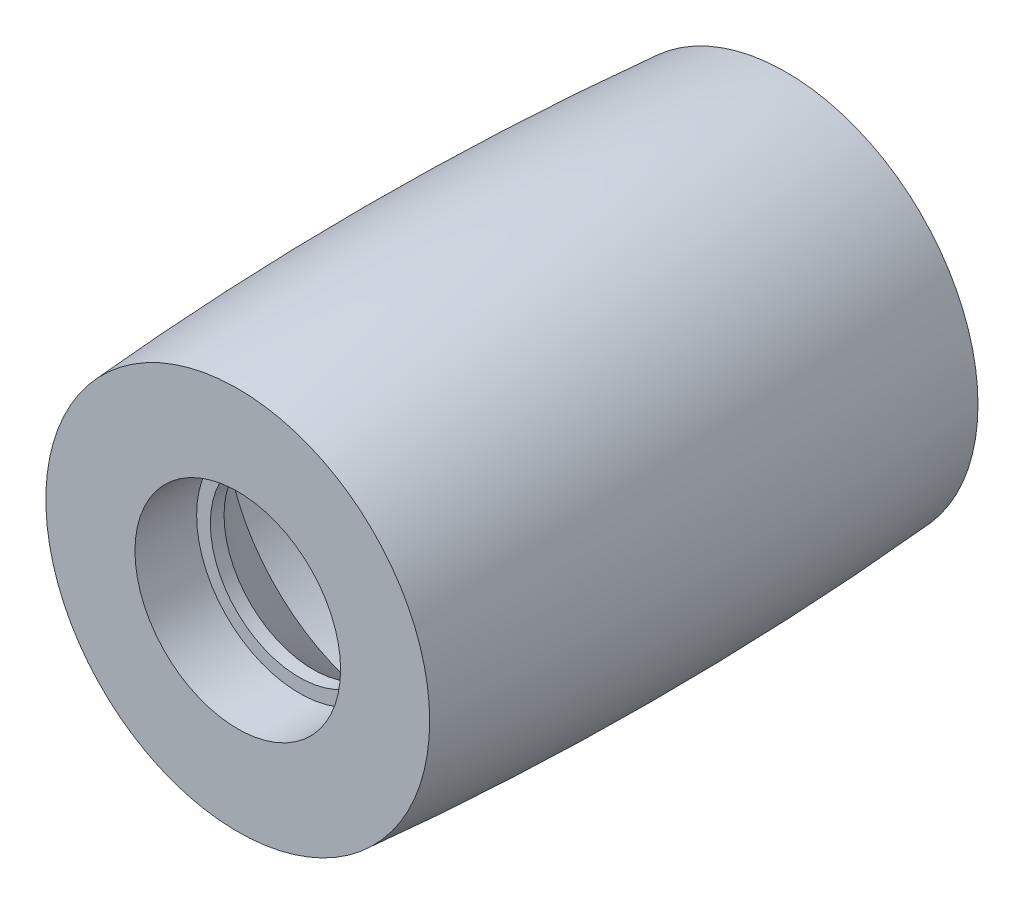
SolidWorks part; units mm, degrees
ref_plane "Ebene vorne" through (0, 0, 0) normal (0, 0, 1) x (1, 0, 0)
ref_plane "Ebene oben" through (0, 0, 0) normal (0, 1, 0) x (1, 0, 0)
ref_plane "Ebene rechts" through (0, 0, 0) normal (1, 0, 0) x (0, 0, -1)
sketch "Skizze1" plane through (440, 0, 0) normal (-1, 0, 0) x (0, 0, 1)
  line L0 (0, 0) -> (-100, 0) construction
  line L1 (-19, 15) -> (-10, 15) construction
  line L2 (-19, 15) -> (-19, 5) construction
  line L3 (-19, 13) -> (-21, 13) construction
  line L4 (-21, 13) -> (-34, 26) construction
  line L5 (-21, 26) -> (-50, 26) construction
  line L6 (-50, 29.5) -> (-50, 26) construction
  line L7 (0, 0) -> (-100, 0) construction
  line L8 (-19, 15) -> (-10, 15)
  line L9 (-19, 15) -> (-19, 13)
  line L10 (-19, 13) -> (-21, 13)
  line L11 (-21, 13) -> (-34, 26)
  line L12 (-34, 26) -> (-50, 26)
  line L13 (-50, 29.5) -> (-50, 26)
  line L14 (-10, 28) -> (-10, 15) construction
  line L15 (-10, 28) -> (-10, 15)
  arc A0 (-10, 28) -> (-90, 28) centre (-50, -504.5833) ccw construction
  arc A1 (-10, 28) -> (-50, 29.5) centre (-50, -504.5833) ccw
revolve "Rotation1" add sketch "Skizze1" angle 360 about L7
mirror "Spiegeln1" about plane through (440, 29.5, -50) normal (0, 0, -1) of bodies 101
